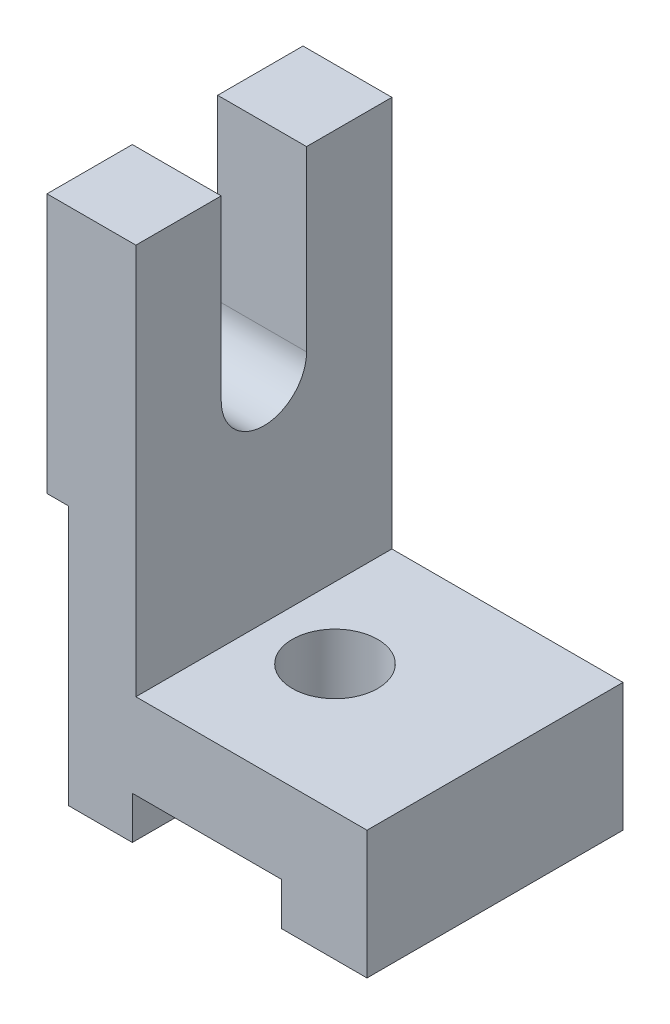
SolidWorks part; units mm, degrees
material "Hexcel AS4C (3000 Filaments)"
ref_plane "Front Plane" through (0, 0, 0) normal (0, 0, 1) x (1, 0, 0)
ref_plane "Top Plane" through (0, 0, 0) normal (0, 1, 0) x (1, 0, 0)
ref_plane "Right Plane" through (0, 0, 0) normal (1, 0, 0) x (0, 0, -1)
sketch "Sketch1" plane through (0, 0, 0) normal (0, 0, 1) x (1, 0, 0)
  line L0 (0, 134) -> (0, -12)
  line L1 (0, -12) -> (24, -12)
  line L2 (24, -12) -> (24, 0)
  line L3 (24, 0) -> (66, 0)
  line L4 (66, 0) -> (66, -12)
  line L5 (66, -12) -> (90, -12)
  line L6 (90, -12) -> (90, 24)
  line L7 (90, 24) -> (25, 24)
  line L8 (25, 24) -> (25, 134)
  line L9 (25, 134) -> (0, 134)
  dimension "D1" = 24
  dimension "D2" = 12
  dimension "D3" = 36
  dimension "D4" = 110
  dimension "D5" = 42
  dimension "D6" = 25
extrude "Boss-Extrude1" add sketch "Sketch1" along normal mid plane 72
sketch "Sketch2" plane through (0, 0, 0) normal (-1, 0, 0) x (0, 0, 1)
  line L0 (36, 134) -> (36, -12) construction
  line L1 (-12, 84) -> (-12, 134)
  line L2 (36, 134) -> (-36, 134) construction
  line L3 (-12, 134) -> (12, 134)
  line L4 (12, 134) -> (12, 84)
  arc A0 (-12, 84) -> (12, 84) centre (0, 84) ccw
  dimension "D1" = 24
  dimension "D3" = 36
  dimension "D2" = 50
extrude "Cut-Extrude1" cut sketch "Sketch2" against normal blind 90
sketch "Sketch3" plane through (0, 0, 0) normal (-1, 0, 0) x (0, 0, 1)
  line L0 (36, -12) -> (-36, -12) construction
  line L1 (-14, -12) -> (68.4909, -12)
  line L2 (-14, -12) -> (-14, 61)
  line L3 (-14, 61) -> (68.4909, 61)
  line L4 (68.4909, -12) -> (68.4909, 61)
  line L5 (36, 134) -> (36, -12) construction
  dimension "D1" = 73
  dimension "D2" = 50
extrude "Cut-Extrude2" cut sketch "Sketch3" against normal blind 6
sketch "Sketch4" plane through (0, -12, 0) normal (0, -1, 0) x (1, 0, 0)
  line L0 (0, 0) -> (90, 0) construction
  line L1 (90, 36) -> (90, -36) construction
  line L2 (90, 0) -> (90.2852, 0.117) construction
  line L3 (45, 36) -> (45, -36) construction
  line L4 (24, 36) -> (66, 36) construction
  line L5 (24, -36) -> (66, -36) construction
  line L6 (66, 36) -> (66, -36) construction
  line L7 (66, 36) -> (66, 11.619)
  line L8 (24, 36) -> (24, -36) construction
  line L9 (24, 36) -> (24, 11.619)
  line L10 (24, -11.619) -> (24, -36)
  line L11 (66, -11.619) -> (66, -36)
  line L12 (24, 36) -> (66, 36)
  line L13 (24, -36) -> (66, -36)
  circle A0 centre (45, 0) radius 12
  arc A1 (24, 11.619) -> (24, -11.619) centre (45, 0) ccw
  arc A2 (66, -11.619) -> (66, 11.619) centre (45, 0) ccw
  dimension "D1" = 24
  dimension "D2" = 48
extrude "Cut-Extrude3" cut sketch "Sketch4" against normal blind 12
extrude "Cut-Extrude4" cut sketch "Sketch4<2>" against normal through all contours A0 region at (45, -12, 0)
sketch "Sketch4<2>" plane through (0, -12, 0) normal (0, -1, 0) x (1, 0, 0) same geometry as "Sketch4"
